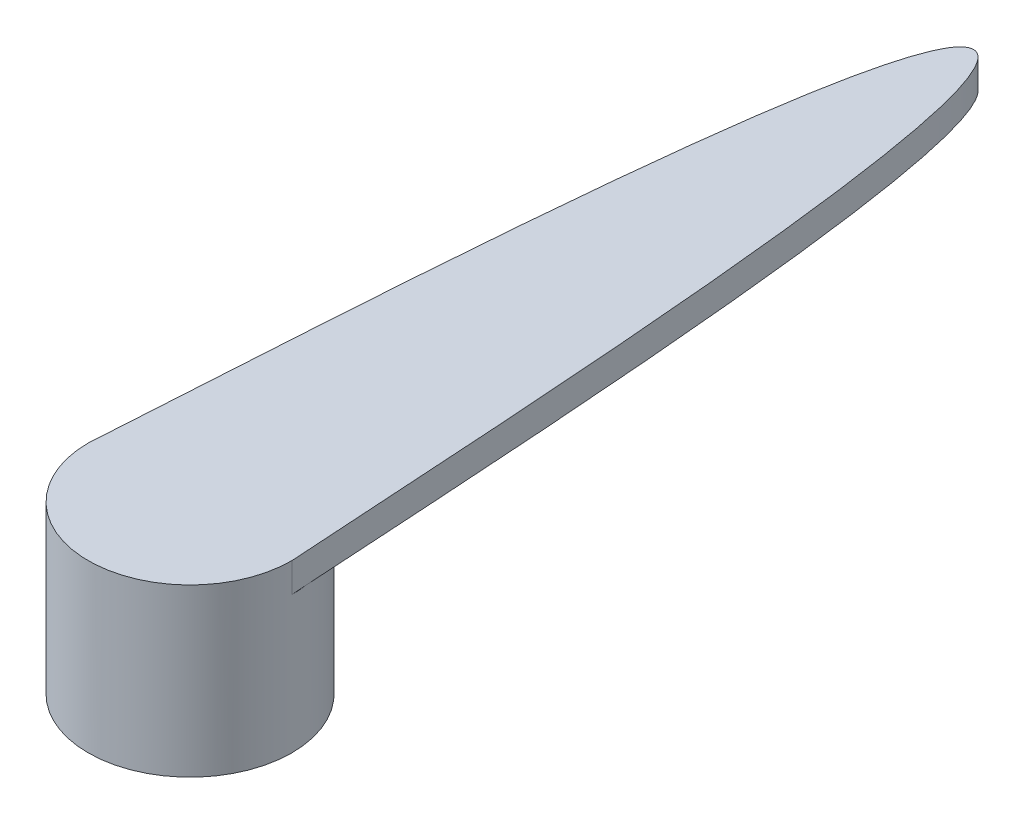
SolidWorks part; units mm, degrees
ref_plane "Piano frontale" through (0, 0, 0) normal (0, 0, 1) x (1, 0, 0)
ref_plane "Piano superiore" through (0, 0, 0) normal (0, 1, 0) x (1, 0, 0)
ref_plane "Piano destro" through (0, 0, 0) normal (1, 0, 0) x (0, 0, -1)
sketch "Schizzo1" plane through (0, 0, 0) normal (0, 1, 0) x (1, 0, 0)
  line L0 (-1.6, 1.6523) -> (-1.6, -1.6523)
  circle A0 centre (0, 0) radius 2.3
  circle A1 centre (0, 0) radius 5.2
  dimension "D1" = 4.6
  dimension "D2" = 1.6
  dimension "D3" = 2.9
extrude "Estrusione-Estrusione1" add sketch "Schizzo1" along normal blind 6 contours A1 A0 | L0 A0 region at (-1.884, 0, 0) region at (-5.0529, 0, 0)
sketch "Schizzo2" plane through (0, 6, 0) normal (0, 1, 0) x (1, 0, 0)
  circle A0 centre (0, 0) radius 5.2
  circle A1 centre (0, 0) radius 5.2 construction
extrude "Estrusione-Estrusione2" add sketch "Schizzo2" along normal blind 1
sketch "Schizzo4" plane through (0, 7, 0) normal (0, 1, 0) x (1, 0, 0)
  line L1 (4.637, 40) -> (-4.637, 40) construction
  line L2 (0, -55) -> (0, 55) construction
  circle A0 centre (0, 0) radius 5.2 construction
  arc A1 (5.2, 0) -> (-5.2, 0) centre (0, 0) cw
  spline S0 degree 3 poles (-5.2, 0) (-4.7066, 6.6863) (-3.2311, 40) (0, 40) knots 0 0 0 0 1 1 1 1
  spline S1 degree 3 poles (5.2, 0) (4.7066, 6.6863) (3.2311, 40) (0, 40) knots 0 0 0 0 1 1 1 1
  dimension "D2" = 40
extrude "Estrusione-Estrusione3" add sketch "Schizzo4" along normal blind 1.5
